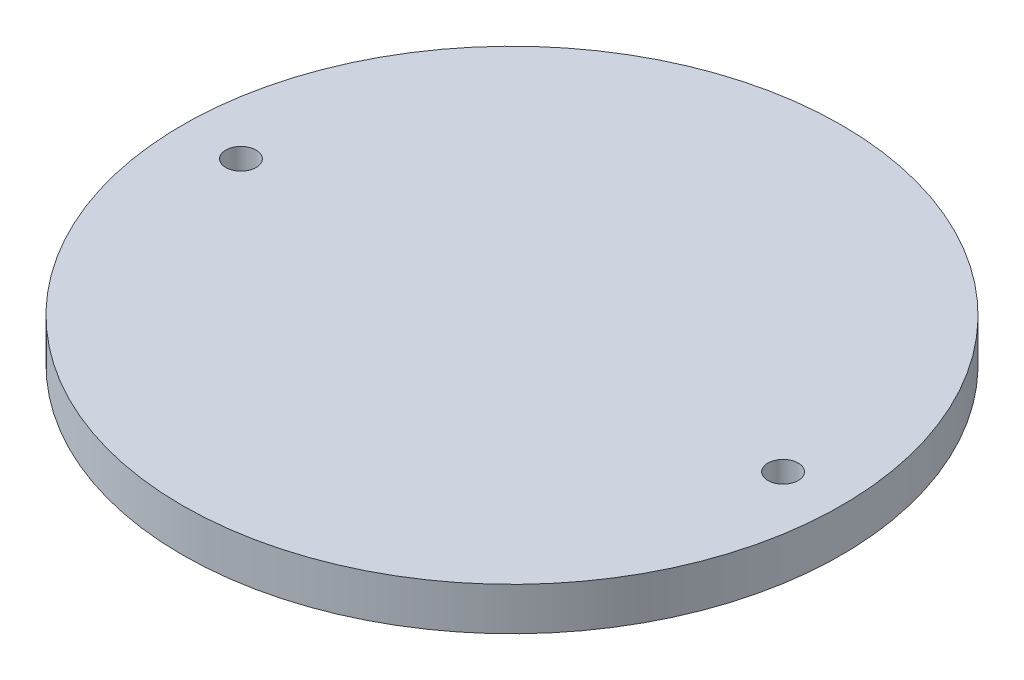
SolidWorks part; units mm, degrees
material "6061 Alloy"
ref_plane "Front Plane" through (0, 0, 0) normal (0, 0, 1) x (1, 0, 0)
ref_plane "Top Plane" through (0, 0, 0) normal (0, 1, 0) x (1, 0, 0)
ref_plane "Right Plane" through (0, 0, 0) normal (1, 0, 0) x (0, 0, -1)
sketch "Sketch2" plane through (0, 0, 0) normal (0, 1, 0) x (1, 0, 0)
  circle A0 centre (0, 0) radius 73.3425
  dimension "D1" = 146.685
extrude "Boss-Extrude1" add sketch "Sketch2" along normal blind 9.525
sketch "Sketch3" plane through (0, 9.525, 0) normal (0, 1, 0) x (1, 0, 0)
  point P0 (-60.325, 0)
  point P1 (60.325, 0)
  dimension "D1" = 60.325
  dimension "D2" = 60.325
hole_wizard "1/4 Clearance Hole1" positions "Sketch3" profile "Sketch4" hole size "1/4" standard "ANSI Inch" end condition through all
sketch "Sketch4" plane through (-60.325, 9.525, 0) normal (1, 0, 0) x (0, 0, 1)
  line L0 (0, 0) -> (0, 9.525)
  line L1 (0, 9.525) -> (3.3782, 9.525)
  line L2 (3.3782, 9.525) -> (3.3782, 0)
  line L5 (3.3782, 0) -> (0, 0)
  line L11 (0, -6.35) -> (0, 107.95) construction
  dimension "Thru Hole Dia." = 6.7564
  dimension "Thru Hole Depth" = 9.525
equation "\"outerdiameter\"= 5.775"
equation "\"D1@Sketch2\"=\"outerdiameter\""
equation "\"platethickness\"= 0.375"
equation "\"holespacing\"= 2.375"
equation "\"D1@Sketch3\"=\"holespacing\""
equation "\"D2@Sketch3\"=\"holespacing\""
